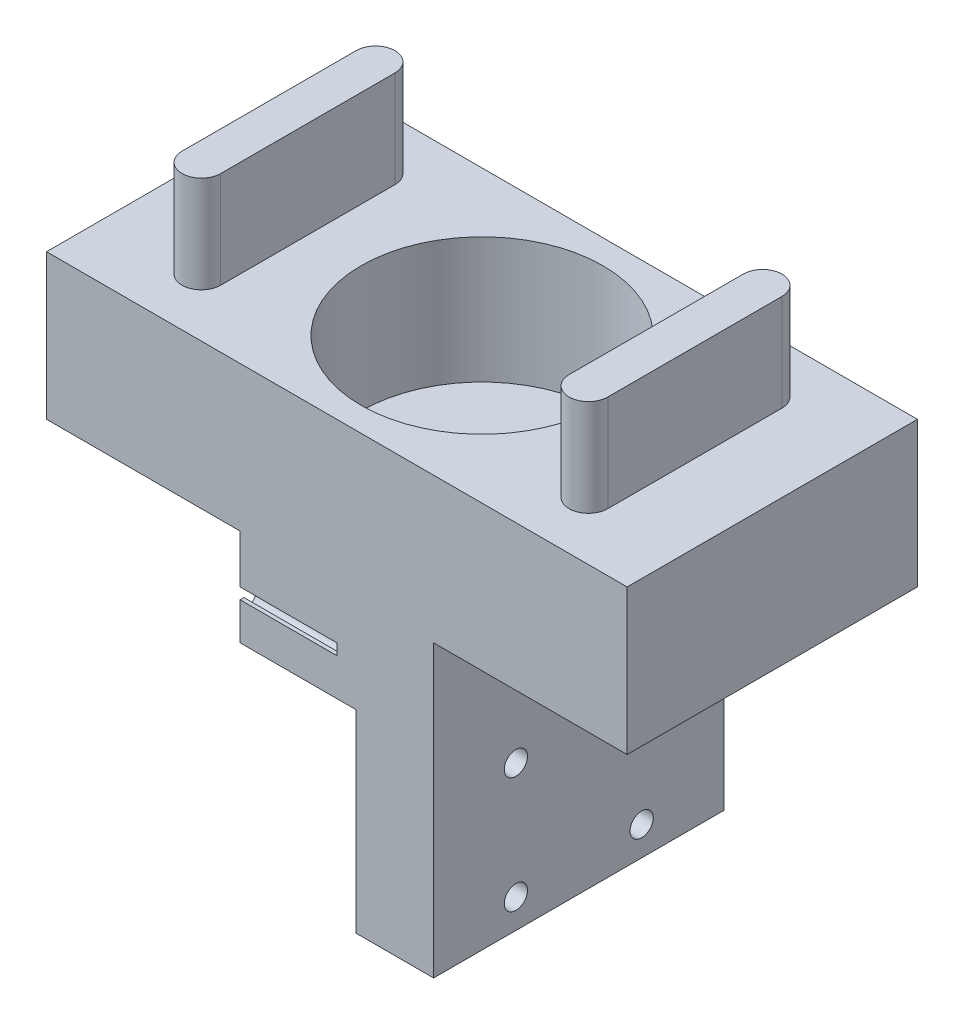
SolidWorks part; units mm, degrees
ref_plane "前视基准面" through (0, 0, 0) normal (0, 0, 1) x (1, 0, 0)
ref_plane "上视基准面" through (0, 0, 0) normal (0, 1, 0) x (1, 0, 0)
ref_plane "右视基准面" through (0, 0, 0) normal (1, 0, 0) x (0, 0, -1)
sketch "草图1" plane through (0, 0, 0) normal (0, 0, 1) x (1, 0, 0)
  line L1 (0, 0) -> (20, 0)
  line L2 (0, 0) -> (0, 30)
  line L3 (0, 30) -> (20, 30)
  line L4 (20, 0) -> (20, 30)
  dimension "D1" = 20
  dimension "D2" = 30
extrude "凸台-拉伸1" add sketch "草图1" along normal blind 30
sketch "草图3" plane through (0, 0, 0) normal (-1, 0, 0) x (0, 0, 1)
  line L0 (15, 0) -> (15, 30) construction
  line L1 (30, 30) -> (30, 0) construction
  line L2 (15, 23) -> (13, 23) construction
  line L4 (0, 30) -> (0, 0) construction
  line L6 (11.6, 23.6) -> (11.6, 23.85)
  line L8 (12.4, 23.85) -> (11.6, 23.85)
  line L9 (12.4, 23.6) -> (12.4, 23.85)
  line L13 (11, 22.0922) -> (11, 23.6062) construction
  line L46 (13, 22.0922) -> (13, 23.9598) construction
  line L47 (9, 22.0922) -> (9, 23.9598) construction
  line L48 (7, 23) -> (9, 23) construction
  line L49 (7.6, 23.6) -> (7.6, 23.85)
  line L50 (8.4, 23.85) -> (7.6, 23.85)
  line L51 (13.6, 23.6) -> (13.6, 23.85)
  line L52 (13.6, 23.85) -> (14.4, 23.85)
  line L53 (14.4, 23.6) -> (14.4, 23.85)
  line L87 (8.4, 23.6) -> (8.4, 23.85)
  line L88 (9.6, 23.6) -> (9.6, 23.85)
  line L89 (9.6, 23.85) -> (10.4, 23.85)
  line L91 (10.4, 23.6) -> (10.4, 23.85)
  line L92 (7, 22.0922) -> (7, 24.2983) construction
  line L93 (3.6, 23.6) -> (3.6, 23.85)
  line L94 (4.4, 23.85) -> (3.6, 23.85)
  line L95 (4.4, 23.6) -> (4.4, 23.85)
  line L96 (5.6, 23.6) -> (5.6, 23.85)
  line L97 (-0.4, 23.6) -> (-0.4, 23.85)
  line L98 (0.4, 23.85) -> (-0.4, 23.85)
  line L99 (0.4, 23.6) -> (0.4, 23.85)
  line L100 (5.6, 23.85) -> (6.4, 23.85)
  line L101 (6.4, 23.6) -> (6.4, 23.85)
  line L102 (1.6, 23.6) -> (1.6, 23.85)
  line L103 (1.6, 23.85) -> (2.4, 23.85)
  line L104 (2.4, 23.6) -> (2.4, 23.85)
  line L105 (-1, 23) -> (-1, 25)
  line L106 (-1, 25) -> (15, 25)
  line L107 (23, 22.0922) -> (23, 24.2983) construction
  line L108 (23, 23) -> (21, 23) construction
  line L109 (21, 22.0922) -> (21, 23.9598) construction
  line L110 (17, 22.0922) -> (17, 23.9598) construction
  line L111 (19, 22.0922) -> (19, 23.6062) construction
  line L112 (15, 23) -> (17, 23) construction
  line L113 (27.6, 23.6) -> (27.6, 23.85)
  line L114 (28.4, 23.85) -> (27.6, 23.85)
  line L115 (28.4, 23.6) -> (28.4, 23.85)
  line L116 (23.6, 23.6) -> (23.6, 23.85)
  line L117 (24.4, 23.85) -> (23.6, 23.85)
  line L118 (29.6, 23.6) -> (29.6, 23.85)
  line L119 (29.6, 23.85) -> (30.4, 23.85)
  line L120 (30.4, 23.6) -> (30.4, 23.85)
  line L121 (24.4, 23.6) -> (24.4, 23.85)
  line L122 (25.6, 23.6) -> (25.6, 23.85)
  line L123 (25.6, 23.85) -> (26.4, 23.85)
  line L124 (26.4, 23.6) -> (26.4, 23.85)
  line L125 (19.6, 23.6) -> (19.6, 23.85)
  line L126 (20.4, 23.85) -> (19.6, 23.85)
  line L127 (20.4, 23.6) -> (20.4, 23.85)
  line L128 (21.6, 23.6) -> (21.6, 23.85)
  line L129 (15.6, 23.6) -> (15.6, 23.85)
  line L130 (16.4, 23.85) -> (15.6, 23.85)
  line L131 (16.4, 23.6) -> (16.4, 23.85)
  line L132 (21.6, 23.85) -> (22.4, 23.85)
  line L133 (22.4, 23.6) -> (22.4, 23.85)
  line L134 (17.6, 23.6) -> (17.6, 23.85)
  line L135 (17.6, 23.85) -> (18.4, 23.85)
  line L136 (18.4, 23.6) -> (18.4, 23.85)
  line L137 (15, 25) -> (31, 25)
  line L138 (31, 25) -> (31, 23)
  line L139 (30, 30) -> (0, 30) construction
  arc A17 (15.6, 23.6) -> (14.4, 23.6) centre (15, 23.6) cw
  arc A24 (13.6, 23.6) -> (12.4, 23.6) centre (13, 23.6) cw
  arc A26 (10.4, 23.6) -> (11.6, 23.6) centre (11, 23.6) ccw
  arc A28 (8.4, 23.6) -> (9.6, 23.6) centre (9, 23.6) ccw
  arc A29 (6.4, 23.6) -> (7.6, 23.6) centre (7, 23.6) ccw
  arc A30 (-1, 23) -> (-0.4, 23.6) centre (-1, 23.6) ccw
  arc A31 (5.6, 23.6) -> (4.4, 23.6) centre (5, 23.6) cw
  arc A32 (3.6, 23.6) -> (2.4, 23.6) centre (3, 23.6) cw
  arc A33 (0.4, 23.6) -> (1.6, 23.6) centre (1, 23.6) ccw
  arc A34 (29.6, 23.6) -> (28.4, 23.6) centre (29, 23.6) cw
  arc A35 (26.4, 23.6) -> (27.6, 23.6) centre (27, 23.6) ccw
  arc A36 (24.4, 23.6) -> (25.6, 23.6) centre (25, 23.6) ccw
  arc A37 (31, 23) -> (30.4, 23.6) centre (31, 23.6) cw
  arc A38 (23.6, 23.6) -> (22.4, 23.6) centre (23, 23.6) cw
  arc A39 (21.6, 23.6) -> (20.4, 23.6) centre (21, 23.6) cw
  arc A40 (19.6, 23.6) -> (18.4, 23.6) centre (19, 23.6) cw
  arc A41 (16.4, 23.6) -> (17.6, 23.6) centre (17, 23.6) ccw
  dimension "D1" = 0.8
  dimension "D3" = 0.6
  dimension "D5" = 5
  dimension "D4" = 0.6
  dimension "D2" = 0.25
  dimension "D6" = 2
extrude "切除-拉伸1" cut sketch "草图3" against normal blind 10
sketch "草图5" plane through (0, 0, 0) normal (-1, 0, 0) x (0, 0, 1)
  line L0 (0, 23.85) -> (0, 0) construction
  line L14 (0, 0) -> (30, 0)
  line L15 (0, 0) -> (0, 20)
  line L16 (0, 20) -> (30, 20)
  line L17 (30, 0) -> (30, 20)
  line L18 (30, 23.85) -> (30, 0) construction
  line L19 (30, 0) -> (0, 0) construction
  dimension "D1" = 20
  dimension "D2" = 0
extrude "切除-拉伸2" cut sketch "草图5" against normal blind 10
hole_wizard "M2 间隙孔1" positions "草图7" profile "草图8" hole size "M2" standard "ISO" end condition through all
sketch "草图7" plane through (0, 0, 0) normal (-1, 0, 0) x (0, 0, 1)
  line L0 (15, 28.8657) -> (15, -1.1343) construction
  line L3 (30, 0) -> (0, 0) construction
  line L4 (0, 30) -> (0, 25) construction
  line L5 (30, 30) -> (30, 25) construction
  point P12 (8.5, 3)
  point P14 (8.5, 15)
  point P29 (21.5, 3)
  point P30 (21.5, 15)
  dimension "D1" = 6.5
  dimension "D2" = 12
  dimension "D3" = 0
  dimension "D4" = 3
sketch "草图8" plane through (0, 15, 21.5) normal (0, 1, 0) x (0, 0, 1)
  line L0 (0, 0) -> (0, 20)
  line L1 (0, 20) -> (1.2, 20)
  line L2 (1.2, 20) -> (1.2, 0.025)
  line L3 (1.2, 0.025) -> (1.225, 0)
  line L5 (1.225, 0) -> (0, 0)
  line L6 (-1.2, 0.025) -> (-1.225, 0) construction
  line L11 (0, -6.35) -> (0, 107.95) construction
  dimension "通孔孔直径" = 2.4
  dimension "通孔孔深度" = 20
  dimension "近端锥形沉头孔直径" = 2.45
  dimension "近端锥形沉头孔角度" = 90
sketch "草图10" plane through (0, 30, 0) normal (0, 1, 0) x (1, 0, 0)
  line L0 (20, -30) -> (0, -30) construction
  line L1 (-20, 0) -> (40, 0)
  line L2 (-20, 0) -> (-20, -30)
  line L3 (-20, -30) -> (40, -30)
  line L4 (40, 0) -> (40, -30)
  line L5 (0, -30) -> (0, 0) construction
  line L7 (20, 0) -> (0, 0) construction
  dimension "D1" = 0
  dimension "D2" = 60
  dimension "D3" = 20
  dimension "D4" = 0
extrude "凸台-拉伸2" add sketch "草图10" along normal blind 15
sketch "草图11" plane through (0, 45, 0) normal (0, 1, 0) x (1, 0, 0)
  line L0 (10, 0) -> (10, -30) construction
  line L4 (-20, 0) -> (-20, -30)
  line L5 (-20, -30) -> (40, -30)
  line L6 (40, -30) -> (40, 0)
  line L7 (40, 0) -> (-20, 0)
  line L8 (-20, 0) -> (-20, -30)
  line L9 (-20, -30) -> (40, -30)
  line L10 (40, -30) -> (40, 0)
  line L11 (40, 0) -> (-20, 0)
  circle A0 centre (10, -15) radius 12.5
  dimension "D2" = 25
  dimension "D1" = 0
extrude "切除-拉伸4" cut sketch "草图11" against normal blind 13 contours L0 A0 | A0 L0 region at (15.3052, 45, 15) region at (4.6948, 45, 15)
sketch "草图12" plane through (0, 45, 0) normal (0, 1, 0) x (1, 0, 0)
  line L0 (10, 0) -> (10, -30) construction
  line L1 (40, 0) -> (-20, 0) construction
  line L2 (-20, -30) -> (40, -30) construction
  line L3 (-20, -15) -> (26.246, -15) construction
  line L5 (-12, -6) -> (-12, -24)
  line L7 (-8, -6) -> (-8, -24)
  line L8 (-20, 0) -> (-20, -30) construction
  line L9 (28, -6) -> (28, -24)
  line L10 (32, -6) -> (32, -24)
  arc A0 (-12, -6) -> (-8, -6) centre (-10, -6) cw
  arc A1 (-12, -24) -> (-8, -24) centre (-10, -24) ccw
  arc A2 (32, -24) -> (28, -24) centre (30, -24) cw
  arc A3 (32, -6) -> (28, -6) centre (30, -6) ccw
  dimension "D4" = 2
  dimension "D1" = 18
  dimension "D2" = 9
  dimension "D3" = 8
extrude "凸台-拉伸4" add sketch "草图12" along normal blind 10
sketch "草图13" plane through (10, 0, 0) normal (-1, 0, 0) x (0, 0, 1)
  line L4 (0, 20) -> (0, 0)
  line L5 (0, 0) -> (30, 0)
  line L6 (30, 0) -> (30, 20)
  line L7 (30, 20) -> (0, 20)
  line L8 (0, 20) -> (0, 0)
  line L9 (0, 0) -> (30, 0)
  line L10 (30, 0) -> (30, 20)
  line L11 (30, 20) -> (0, 20)
  circle A0 centre (8.5, 15) radius 2.5
  circle A1 centre (21.5, 15) radius 2.5
  circle A2 centre (21.5, 3) radius 2.5
  circle A3 centre (8.5, 3) radius 2.5
  line M10 (0, 20) -> (0, 0)
  line M11 (0, 0) -> (30, 0)
  line M12 (30, 0) -> (30, 20)
  line M13 (30, 20) -> (0, 20)
  dimension "D1" = 5
  dimension "D2" = 5
  dimension "D3" = 5
  dimension "D4" = 5
  dimension "D5" = 0
extrude "切除-拉伸5" cut sketch "草图13" against normal blind 2 contours A3 A2 A1 A0 M13 M10 M11 M12 region at (10, 10.1506, 15)
